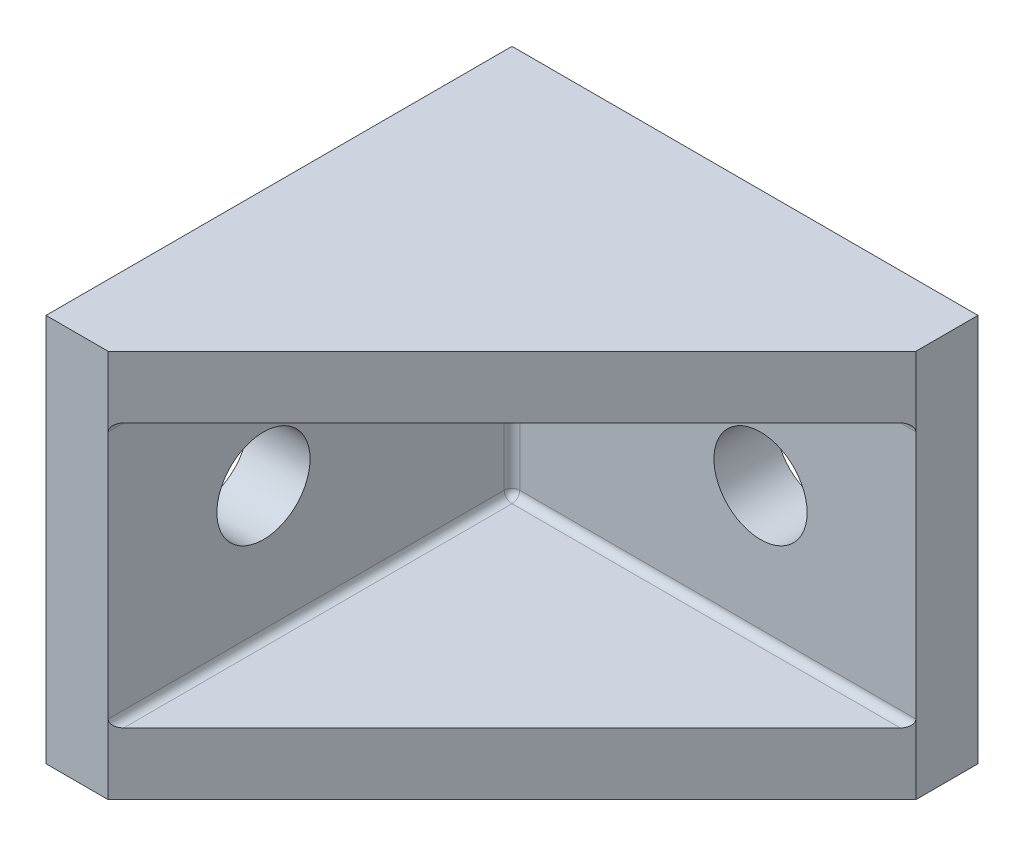
SolidWorks part; units mm, degrees
material "7075-T6, Płyta (SS)"
ref_plane "Płaszczyzna XY" through (0, 0, 0) normal (0, 0, 1) x (1, 0, 0)
ref_plane "Płaszczyzna XZ" through (0, 0, 0) normal (0, 1, 0) x (1, 0, 0)
ref_plane "Płaszczyzna YZ" through (0, 0, 0) normal (1, 0, 0) x (0, 0, -1)
sketch "Szkic1" plane through (0, 0, 0) normal (0, 1, 0) x (1, 0, 0)
  line L4 (0, 0) -> (0, -30)
  line L5 (0, 0) -> (30, 0)
  line L6 (30, -4) -> (4, -30)
  line L7 (0, -30) -> (4, -30)
  line L8 (30, -4) -> (30, 0)
  line L9 (0, -30) -> (0, -34) construction
  line L10 (4, -30) -> (0, -34) construction
  dimension "D1" = 30
  dimension "D2" = 30
  dimension "D3" = 4
  dimension "D4" = 4
extrude "Dodanie-wyciągnięcie1" add sketch "Szkic1" along normal mid plane 25
shell "Skorupa1" thickness 4 removed face at (17, 0, 17) removed face at (2, 0, 30) removed face at (30, 0, 2)
sketch "Szkic2" plane through (4, 0, 0) normal (1, 0, 0) x (0, 0, -1)
  line L0 (-30, 8.5) -> (-30, -8.5) construction
  circle A0 centre (-20, 0) radius 3
  dimension "D4" = 6
  dimension "D5" = 0
  dimension "D1" = 10
extrude "Wytnij-wyciągnięcie1" cut sketch "Szkic2" against normal blind 50
sketch "Szkic3" plane through (0, 0, 4) normal (0, 0, 1) x (1, 0, 0)
  line L1 (30, 8.5) -> (30, -8.5) construction
  circle A0 centre (20, 0) radius 3
  circle A1 centre (18, 24.9199) radius 4
  dimension "D2" = 0
  dimension "D3" = 6
  dimension "D4" = 8
  dimension "D5" = 10
  dimension "D1" = 25
  dimension "D6" = 12
extrude "Wytnij-wyciągnięcie2" cut sketch "Szkic3" against normal blind 50
fillet "Zaokrąglenie1" radius 0.5 5 edges at (17, 8.5, 4) (4, 8.5, 17) (17, -8.5, 4) (4, -8.5, 17) (4, 0, 4)
